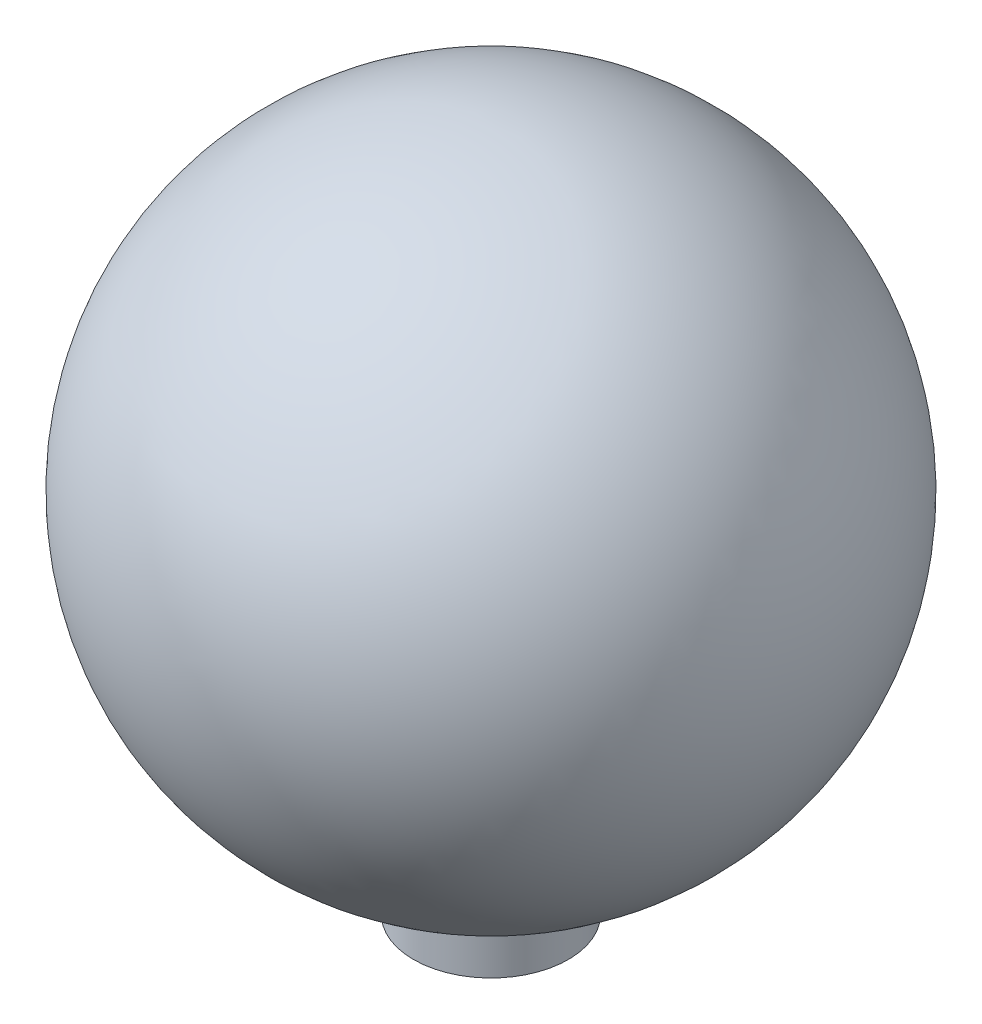
SolidWorks part; units mm, degrees
material "ABS"
ref_plane "Front Plane" through (0, 0, 0) normal (0, 0, 1) x (1, 0, 0)
ref_plane "Top Plane" through (0, 0, 0) normal (0, 1, 0) x (1, 0, 0)
ref_plane "Right Plane" through (0, 0, 0) normal (1, 0, 0) x (0, 0, -1)
sketch "Sketch1" plane through (0, 0, 0) normal (0, 1, 0) x (1, 0, 0)
  circle A0 centre (0, 0) radius 3.175
  dimension "D1" = 6.35
extrude "Boss-Extrude1" add sketch "Sketch1" along normal blind 2.54
dome "Dome1" faces to dome 1 distance 25.4 reverse direction no elliptical dome no face at (0, 2.54, 3.175) parameters "D1"=25.4
sketch "Sketch8" plane through (0, 0, 0) normal (0, -1, 0) x (1, 0, 0)
  circle A0 centre (0, 0) radius 1.5875
  dimension "D1" = 3.175
extrude "Cut-Extrude1" cut sketch "Sketch8" against normal blind 6.35
hole_wizard "#4 (0.209) Diameter Hole1" positions "Sketch7" profile "Sketch6" hole size "#4" standard "ANSI Inch"
sketch "Sketch7" plane through (0, 0, 0) normal (0, -1, 0) x (-1, 0, 0)
  point P0 (0, 0)
sketch "Sketch6" plane through (0, 0, 0) normal (1, 0, 0) x (0, 0, -1)
  line L0 (0, 0) -> (0, 7.9449)
  line L1 (0, 7.9449) -> (2.6543, 6.35)
  line L2 (2.6543, 6.35) -> (2.6543, 0)
  line L5 (2.6543, 0) -> (0, 0)
  line L10 (0, 7.9449) -> (-2.6543, 6.35) construction
  line L11 (0, -6.35) -> (0, 107.95) construction
  dimension "Hole Dia." = 5.3086
  dimension "Hole Depth" = 6.35
  dimension "Drill Angle" = 118
